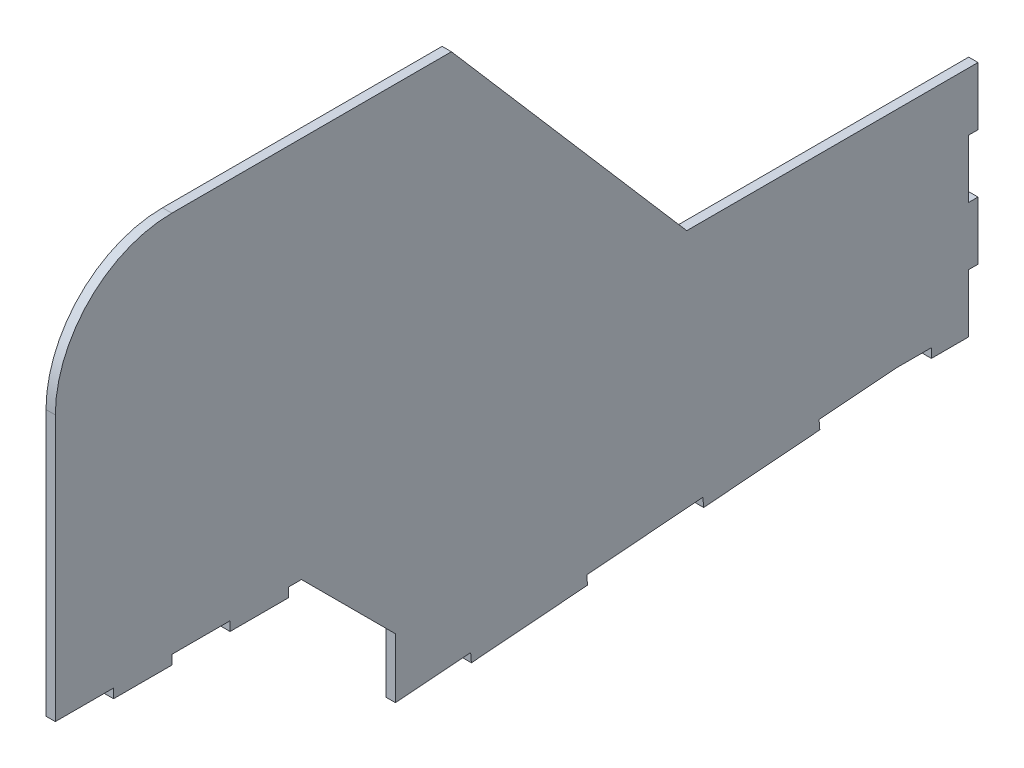
SolidWorks part; units mm, degrees
ref_plane "Alzado" through (0, 0, 0) normal (0, 0, 1) x (1, 0, 0)
ref_plane "Planta" through (0, 0, 0) normal (0, 1, 0) x (1, 0, 0)
ref_plane "Vista lateral" through (0, 0, 0) normal (1, 0, 0) x (0, 0, -1)
sketch "Croquis2" plane through (0, 0, 0) normal (1, 0, 0) x (0, 0, -1)
  line L0 (-196, -75) -> (-90.3534, -75)
  line L1 (-200, 150) -> (200, 150) construction
  line L2 (-200, 150) -> (-200, -150) construction
  line L3 (-200, -150) -> (200, -150) construction
  line L4 (200, 150) -> (200, -150) construction
  line L5 (-200, 150) -> (200, -150) construction
  line L6 (-200, -150) -> (200, 150) construction
  line L11 (-90.3534, -75) -> (-28.5398, -75) construction
  line L17 (-90.3534, -75) -> (-50, -115.3534)
  line L18 (-50, -115.3534) -> (-50, -145)
  line L19 (-50, -145) -> (165, -128)
  line L20 (165, -128) -> (200, -128)
  line L21 (200, -128) -> (200, -28)
  line L22 (200, -28) -> (75, -28)
  line L23 (75, -28) -> (-26, 89)
  line L24 (-26, 89) -> (-196, 89)
  line L25 (-196, 89) -> (-196, -75)
  point P0 (0, 0)
  point P10 (2, 0)
  dimension "D1" = 400
  dimension "D2" = 300
  dimension "D3" = 4
  dimension "D4" = 75
  dimension "D6" = 22
  dimension "D7" = 35
  dimension "D5" = 5
  dimension "D8" = 150
  dimension "D9" = 45
  dimension "D10" = 100
  dimension "D11" = 170
  dimension "D12" = 275
  dimension "D13" = 164
extrude "Saliente-Extruir1" add sketch "Croquis2" along normal blind 4 contours L0 L17 L18 L19 L20 L21 L22 L23 L24 L25 | L0 | L0 region at (0, -32.3047, 18.9642)
sketch "Croquis3" plane through (4, 0, 0) normal (1, 0, 0) x (0, 0, -1)
  line L0 (200, -128) -> (200, -28) construction
  line L1 (200, -53) -> (196, -53)
  line L2 (200, -53) -> (200, -78)
  line L3 (200, -78) -> (196, -78)
  line L4 (196, -53) -> (196, -78)
  line L5 (200, -53) -> (196, -78) construction
  line L6 (200, -78) -> (196, -53) construction
  line L7 (200, -28) -> (200, -53) construction
  line L8 (200, -103) -> (196, -103)
  line L9 (200, -103) -> (200, -128)
  line L10 (200, -128) -> (196, -128)
  line L11 (196, -103) -> (196, -128)
  line L12 (200, -103) -> (196, -128) construction
  line L13 (200, -128) -> (196, -103) construction
  line L14 (200, -78) -> (200, -103) construction
  point P4 (198, -65.5)
  point P11 (198, -115.5)
  dimension "D1" = 25
  dimension "D2" = 4
extrude "Cortar-Extruir1" cut sketch "Croquis3" against normal blind 10
sketch "Croquis4" plane through (4, 0, 0) normal (1, 0, 0) x (0, 0, -1)
  line L0 (-196, -75) -> (-171, -75)
  line L1 (-196, -75) -> (-90.3534, -75) construction
  line L2 (-171, -75) -> (-171, -79)
  line L3 (-171, -79) -> (-146, -79)
  line L4 (-146, -79) -> (-146, -75)
  line L5 (-146, -75) -> (-121, -75)
  line L6 (-121, -75) -> (-121, -79)
  line L7 (-121, -79) -> (-96, -79)
  line L8 (-96, -79) -> (-96, -75)
  line L9 (-96, -75) -> (-71, -75)
  line L10 (-90.3534, -75) -> (-28.5398, -75) construction
  line L11 (-71, -75) -> (-71, -79)
  line L12 (-71, -79) -> (-46, -79)
  line L13 (-46, -79) -> (-46, -75)
  line L14 (-46, -75) -> (-21, -75)
  line L15 (-21, -75) -> (-21, -79)
  line L16 (-21, -79) -> (4, -79)
  line L17 (4, -79) -> (4, -43.9665)
  line L18 (4, -43.9665) -> (4, -42.5047)
  line L19 (4, -42.5047) -> (-196, -42.5047)
  line L20 (-196, 89) -> (-196, -75) construction
  line L21 (-196, -42.5047) -> (-196, -75)
  dimension "D1" = 25
  dimension "D2" = 4
extrude "Saliente-Extruir2" add sketch "Croquis4" against normal blind 4
sketch "Croquis5" plane through (4, 0, 0) normal (1, 0, 0) x (0, 0, -1)
  line L1 (180, -128) -> (165, -128)
  line L2 (180, -128) -> (180, -124)
  line L3 (180, -124) -> (165, -124)
  line L4 (165, -128) -> (165, -124)
  line L5 (180, -128) -> (165, -124) construction
  line L6 (180, -124) -> (165, -128) construction
  point P4 (172.5, -126)
  dimension "D2" = 4
  dimension "D1" = 15
  dimension "D3" = 20
extrude "Cortar-Extruir2" cut sketch "Croquis5" against normal blind 10
sketch "Croquis6" plane through (4, 0, 0) normal (1, 0, 0) x (0, 0, -1)
  line L0 (165, -128) -> (132.1027, -130.6012)
  line L2 (132.1027, -130.6012) -> (131.7864, -126.6012)
  line L3 (164.6837, -124) -> (131.7864, -126.6012)
  line L4 (-50, -145) -> (165, -128) construction
  line L5 (82.2582, -134.5424) -> (32.4138, -138.4836)
  line L6 (82.2582, -134.5424) -> (81.942, -130.5424)
  line L7 (32.4138, -138.4836) -> (32.0975, -134.4836)
  line L8 (81.942, -130.5424) -> (32.0975, -134.4836)
  line L9 (-50.3279, -145.0259) -> (-17.4306, -142.4247)
  line L10 (-50.3279, -145.0259) -> (-50.6442, -141.0259)
  line L11 (-17.4306, -142.4247) -> (-17.7469, -138.4247)
  line L12 (-50.6442, -141.0259) -> (-17.7469, -138.4247)
  line L14 (165, -128) -> (167.0673, -128)
  line L15 (165, -124) -> (167.0673, -124)
  line L16 (167.0673, -128) -> (167.0673, -124)
  line L17 (164.6837, -124) -> (165, -124)
  dimension "D1" = 33
  dimension "D2" = 50
  dimension "D3" = 50
  dimension "D4" = 50
  dimension "D5" = 4
extrude "Cortar-Extruir3" cut sketch "Croquis6" against normal blind 10
sketch "Croquis7" plane through (4, 0, 0) normal (1, 0, 0) x (0, 0, -1)
  line L0 (-146, 39) -> (-196, 39) construction
  line L1 (-196, 89) -> (-196, -75) construction
  line L3 (-196, 89) -> (-109.4016, 89)
  line L4 (-196, 89) -> (-196, 4.9331)
  line L5 (-196, 4.9331) -> (-109.4016, 4.9331)
  line L6 (-109.4016, 89) -> (-109.4016, 4.9331)
  line L7 (-196, 89) -> (-109.4016, 4.9331) construction
  line L8 (-196, 4.9331) -> (-109.4016, 89) construction
  circle A0 centre (-146, 39) radius 50
  point P12 (-152.7008, 46.9665)
  line M17 (-196, 89) -> (-196, -75)
  dimension "D1" = 100
  dimension "D2" = 118
extrude "Cortar-Extruir4" cut sketch "Croquis7" against normal through all contours A0 L3 M17 region at (4, 77.8316, 184.8316)
equation "\"venesta\"= 4'grosor de la venesta"
equation "\"policarbonato\"= 4'grosor del policarbonato"
equation "\"carton_trupan\"= 3'grosor del carton trupan caso laser"
equation "\"ancho_tot\"= 310'ancho tot sin llantas"
equation "\"largo_tot\"= 400'largo tot sin camera"
equation "\"alto_estimado\"= 300'alto estimado sin lidar"
equation "\"D2@Croquis2\"=\"alto_estimado\""
equation "\"D1@Croquis2\"=\"largo_tot\""
equation "\"altoparaqpaselabotella\"= 75'alto estimado para que encaje la botella"
equation "\"alturaruedaloca\"= 22"
equation "\"anchoruedaloca\"= 35"
equation "\"anchopiso1motorybaterias\"= 150"
equation "\"dist-pisorampa\"= 5"
equation "\"D3@Croquis2\"=\"venesta\""
equation "\"D4@Croquis2\"=\"altoparaqpaselabotella\""
equation "\"D6@Croquis2\"=\"alturaruedaloca\""
equation "\"D7@Croquis2\"=\"anchoruedaloca\""
equation "\"D5@Croquis2\"=\"dist-pisorampa\""
equation "\"D8@Croquis2\"=\"anchopiso1motorybaterias\""
equation "\"D10@Croquis2\"= \"paredtrasera\""
equation "\"D11@Croquis2\" = \"anchoultimopiso\""
equation "\"anchoultimopiso\"= 170"
equation "\"paredtrasera\"= 100"
equation "\"agarradorcanasta\"= 275'recolector"
equation "\"D12@Croquis2\"=\"agarradorcanasta\""
equation "\"D13@Croquis2\"= \"alturapiso1y2\" + \"venesta\" + \"alturapiso2y3\""
equation "\"alturapiso1y2\"= 80"
equation "\"alturapiso2y3\"= 80"
equation "\"D1@Saliente-Extruir1\"=\"policarbonato\""
equation "\"D2@Croquis3\"=\"policarbonato\""
equation "\"D2@Croquis4\"=\"venesta\""
equation "\"D1@Saliente-Extruir2\"=\"policarbonato\""
equation "\"D2@Croquis5\"=\"venesta\""
equation "\"D5@Croquis6\"=\"venesta\""
